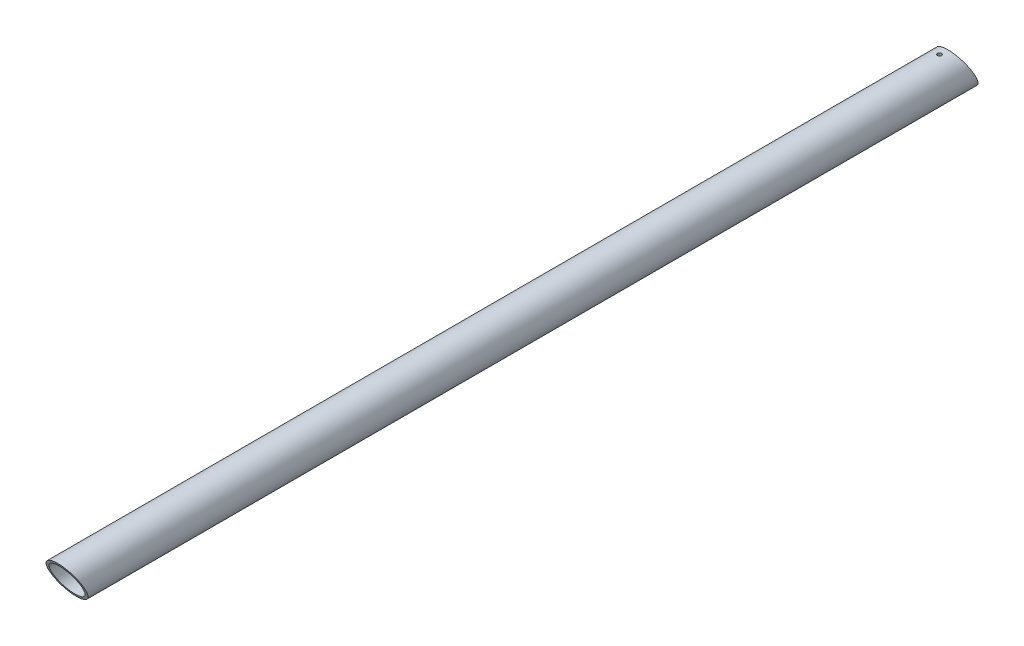
SolidWorks part; units mm, degrees
ref_plane "front" through (0, 0, 0) normal (0, 0, 1) x (1, 0, 0)
ref_plane "top" through (0, 0, 0) normal (0, 1, 0) x (1, 0, 0)
ref_plane "right" through (0, 0, 0) normal (1, 0, 0) x (0, 0, -1)
ref_axis "Axis1" through (0, 0, -785.3149) along (0, 0, 1)
sketch "Sketch3" plane through (0, 0, 0) normal (1, 0, 0) x (0, 0, -1)
  line L0 (-861.441, 0) -> (861.441, 0) construction
  line L2 (-879.386, 36.5125) -> (-843.496, -36.5125)
  line L5 (843.496, 36.5125) -> (879.386, -36.5125)
  line L6 (-879.386, 36.5125) -> (-879.386, 378.6423) construction
  dimension "D1" = 1722.882
  dimension "D2" = 26.173
  dimension "D3" = 73.025
  dimension "D4" = 1546.2286
  dimension "D5" = 63.827
sketch "Sketch1" plane through (0, 0, 0) normal (0, 0, 1) x (1, 0, 0)
  circle A0 centre (0, 0) radius 36.5125
  circle A1 centre (0, 0) radius 31.3563
  dimension "D1" = 5.1562
  dimension "D2" = 73.025
extrude "Base-Extrude" add sketch "Sketch1" along normal mid plane 1828.8
sketch "Sketch6" plane through (0, 0, 0) normal (1, 0, 0) x (0, 0, -1)
  line L1 (-956.1526, 192.7085) -> (-746.9641, -232.9248)
  line L3 (766.7294, 192.7085) -> (975.9179, -232.9248)
  line L4 (-956.1526, 192.7085) -> (-956.1526, -232.9248)
  line L5 (-956.1526, -232.9248) -> (-746.9641, -232.9248)
  line L6 (766.7294, 192.7085) -> (975.9179, 192.7085)
  line L7 (975.9179, 192.7085) -> (975.9179, -232.9248)
  line L8 (-879.386, 36.5125) -> (-843.496, -36.5125) construction
  line L9 (843.496, 36.5125) -> (879.386, -36.5125) construction
extrude "Cut-Extrude5" cut sketch "Sketch6" against normal mid plane 152.4
sketch "Sketch4" plane through (0, 0, 0) normal (0, 1, 0) x (1, 0, 0)
  circle A0 centre (0, 863.6) radius 3.9751
  dimension "D2" = 7.9502
  dimension "D1" = 863.6
extrude "Cut-Extrude2" cut sketch "Sketch4" against normal mid plane 127
sketch "Sketch5" plane through (0, 0, 0) normal (0, 1, 0) x (1, 0, 0)
  circle A0 centre (0, 827.621) radius 3.9751
  ellipse E0 centre (0, 861.441) end of major axis (-36.5125, 861.441) minor radius 17.945 construction
  point P2 (0, 843.496)
  dimension "D1" = 7.9502
  dimension "D2" = 827.621
  dimension "D3" = 15.875
extrude "Cut-Extrude3" cut sketch "Sketch5" along normal through all
